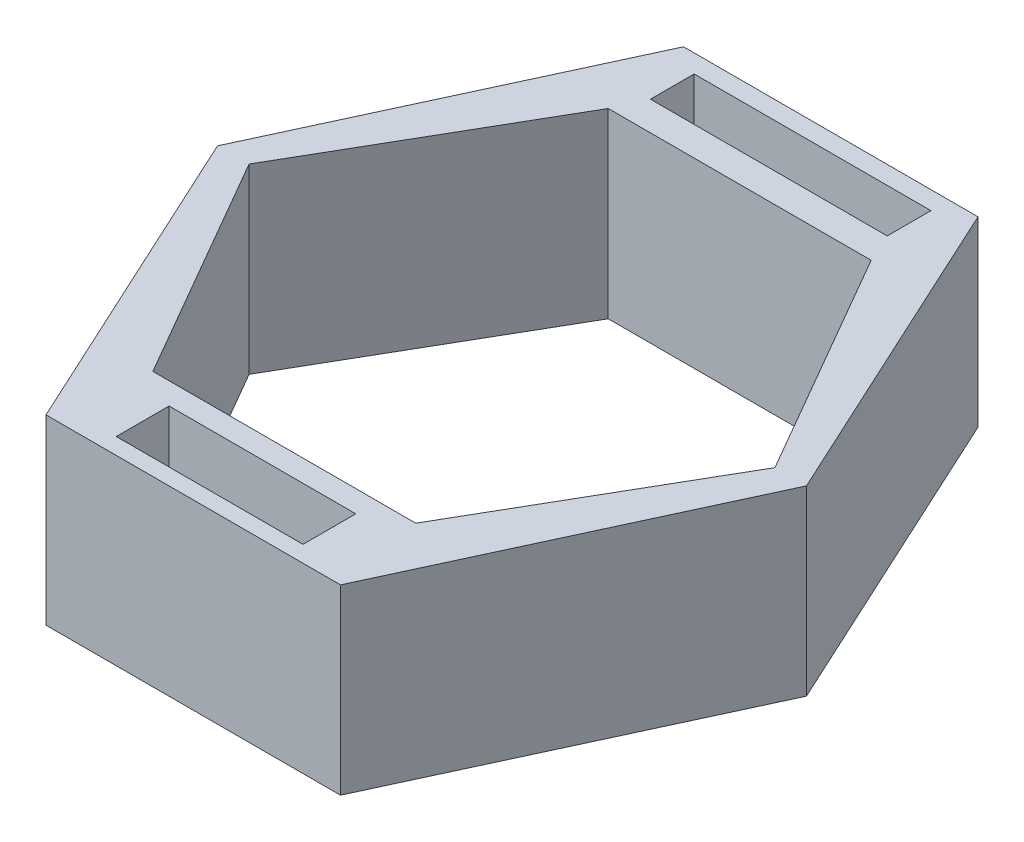
SolidWorks part; units mm, degrees
ref_plane "Front Plane" through (0, 0, 0) normal (0, 0, 1) x (1, 0, 0)
ref_plane "Top Plane" through (0, 0, 0) normal (0, 1, 0) x (1, 0, 0)
ref_plane "Right Plane" through (0, 0, 0) normal (1, 0, 0) x (0, 0, -1)
sketch "Sketch1" plane through (0, 0, 0) normal (0, 1, 0) x (1, 0, 0)
  line L0 (32.3316, 0) -> (16.1658, 28)
  line L1 (28.8675, 0) -> (14.4338, 25)
  line L2 (14.4338, 25) -> (-14.4338, 25)
  line L3 (-14.4338, 25) -> (-28.8675, 0)
  line L4 (-28.8675, 0) -> (-14.4338, -25)
  line L5 (-14.4338, -25) -> (14.4338, -25)
  line L6 (14.4338, -25) -> (28.8675, 0)
  line L7 (16.1658, 28) -> (-16.1658, 28)
  line L8 (-16.1658, 28) -> (-32.3316, 0)
  line L9 (-32.3316, 0) -> (-16.1658, -28)
  line L10 (-16.1658, -28) -> (16.1658, -28)
  line L11 (16.1658, -28) -> (32.3316, 0)
  line L12 (-16.1658, 35) -> (-32.3316, 0)
  line L13 (-16.1658, -28) -> (16.1658, -28)
  line L14 (-16.1658, -28) -> (-16.1658, -35)
  line L15 (-16.1658, -35) -> (16.1658, -35)
  line L16 (16.1658, -28) -> (16.1658, -35)
  line L17 (-16.1658, 28) -> (16.1658, 28)
  line L18 (-16.1658, 28) -> (-16.1658, 35)
  line L19 (-16.1658, 35) -> (16.1658, 35)
  line L20 (16.1658, 28) -> (16.1658, 35)
  line L21 (-16.1658, -35) -> (-32.3316, 0)
  line L22 (16.1658, 35) -> (32.3316, 0)
  line L23 (16.1658, -35) -> (32.3316, 0)
  circle A0 centre (0, 0) radius 25 construction
  dimension "D1" = 50
  dimension "D3" = 7
  dimension "D4" = 7
  dimension "D2" = 3
extrude "Boss-Extrude1" add sketch "Sketch1" along normal blind 20 contours L10 L11 L0 L7 L8 L9 L6 L5 L4 L3 L2 L1 | L7 L20 L19 L18 | L8 L18 L12 | L22 L20 L0 | L16 L23 L11 | L16 L10 L14 L15 | L21 L14 L9 region at (23.5079, 0, 13.5723) region at (21.5544, 0, 21) region at (21.5544, 0, -21) region at (0, 0, -31.5) region at (0, 0, 31.5) region at (-21.5544, 0, -21) region at (-21.5544, 0, 21)
sketch "Sketch2" plane through (0, 20, 0) normal (0, 1, 0) x (1, 0, 0)
  line L0 (-14.4338, -25) -> (14.4338, -25) construction
  line L1 (-13, 33) -> (13, 33)
  line L2 (-13, 33) -> (-13, 28.2)
  line L3 (-13, 28.2) -> (13, 28.2)
  line L4 (13, 33) -> (13, 28.2)
  line L5 (-10.25, -27.4) -> (10.25, -27.4)
  line L6 (-10.25, -27.4) -> (-10.25, -33.2)
  line L7 (-10.25, -33.2) -> (10.25, -33.2)
  line L8 (10.25, -27.4) -> (10.25, -33.2)
  line L9 (-16.1658, 35) -> (16.1658, 35) construction
  point P8 (0, -27.4)
  point P10 (0, 28.2)
  dimension "D1" = 26
  dimension "D2" = 20.5
  dimension "D3" = 4.8
  dimension "D4" = 5.8
  dimension "D5" = 2.4
  dimension "D6" = 2
extrude "Cut-Extrude1" cut sketch "Sketch2" against normal blind 17 contours L8 L5 L6 L7 region at (0, 20, 30.3)
extrude "Cut-Extrude2" cut sketch "Sketch2<3>" against normal blind 26 contours L4 L1 L2 L3 region at (0, 20, -30.6)
sketch "Sketch2<3>" plane through (0, 20, 0) normal (0, 1, 0) x (1, 0, 0) same geometry as "Sketch2"
